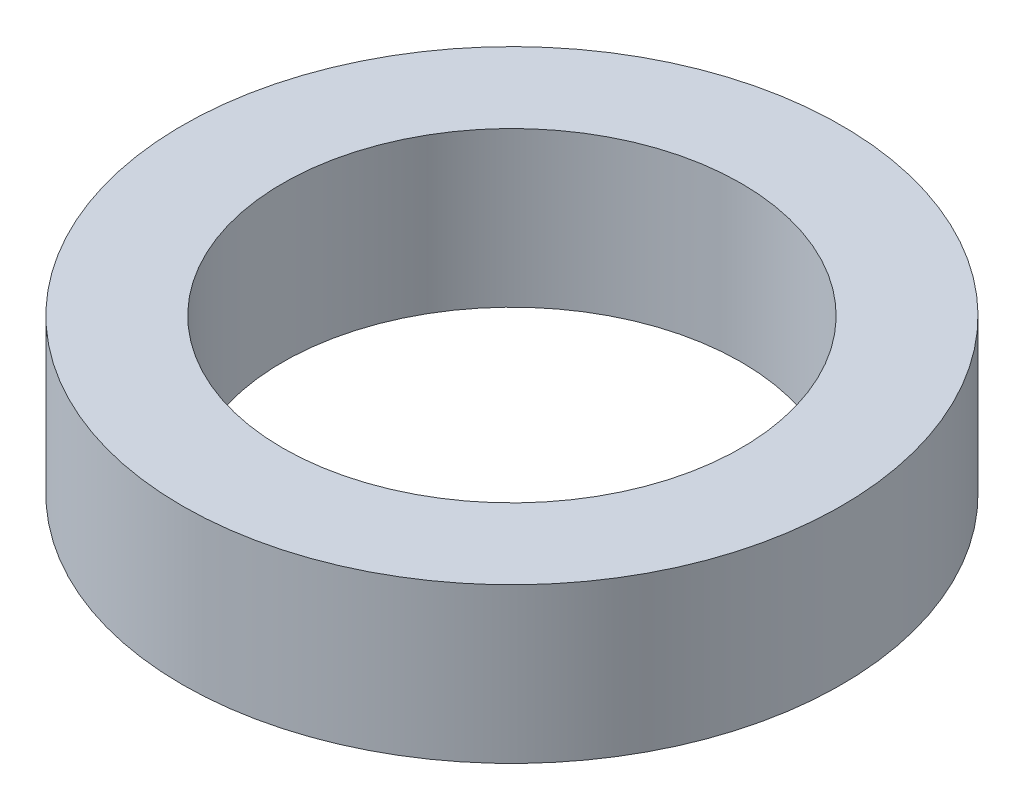
SolidWorks part; units mm, degrees
ref_plane "Front Plane" through (0, 0, 0) normal (0, 0, 1) x (1, 0, 0)
ref_plane "Top Plane" through (0, 0, 0) normal (0, 1, 0) x (1, 0, 0)
ref_plane "Right Plane" through (0, 0, 0) normal (1, 0, 0) x (0, 0, -1)
sketch "Sketch1" plane through (0, 0, 0) normal (0, 1, 0) x (1, 0, 0)
  circle A0 centre (0, 0) radius 57.5
  dimension "FLANGE_OD" = 115
extrude "Boss-Extrude1" add sketch "Sketch1" along normal blind 27
sketch "Sketch2" plane through (0, 0, 0) normal (0, 1, 0) x (1, 0, 0)
  circle A0 centre (0, 0) radius 40
  dimension "BORE_D" = 80
extrude "Cut-Extrude1" cut sketch "Sketch2" along normal through all
sketch "Sketch3" plane through (0, 27, 0) normal (0, 1, 0) x (1, 0, 0)
  circle A0 centre (0, 0) radius 24.6559 construction
  circle A1 centre (-24.6559, 0) radius 2.9199
  dimension "BOLT_D" = 5.8399
  dimension "BOLT_PCD" = 49.3119
extrude "Cut-Extrude2" cut sketch "Sketch3" against normal blind 25.9122 rebuild error yes
pattern_circular "CirPattern1" count 8 over 360 rebuild error yes
